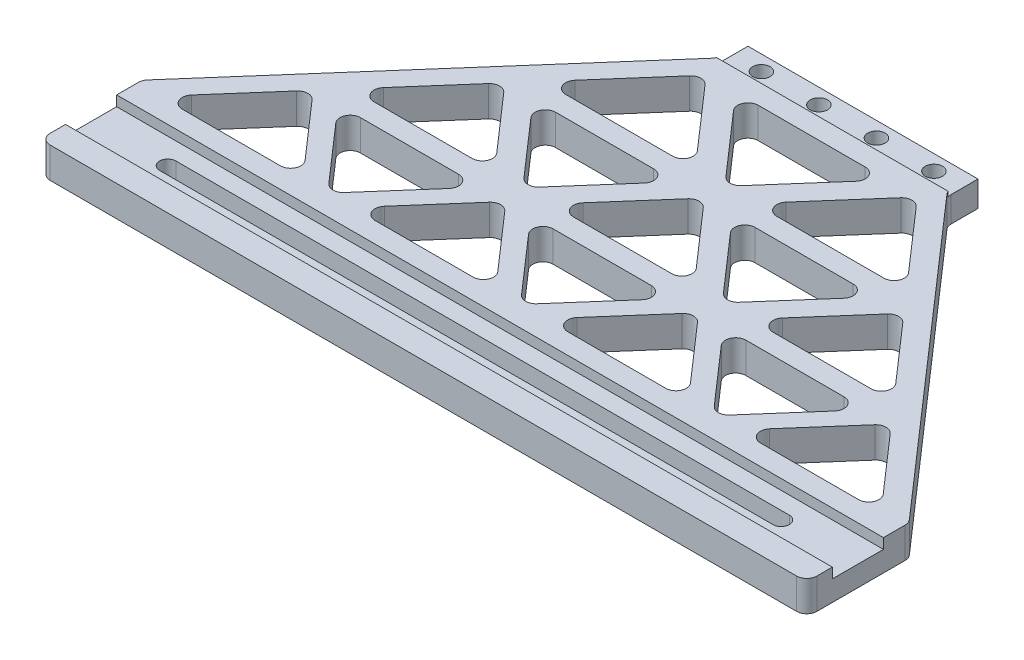
SolidWorks part; units mm, degrees
material "Сплав 2024"
ref_plane "Спереди" through (0, 0, 0) normal (0, 0, 1) x (1, 0, 0)
ref_plane "Сверху" through (0, 0, 0) normal (0, 1, 0) x (1, 0, 0)
ref_plane "Справа" through (0, 0, 0) normal (1, 0, 0) x (0, 0, -1)
sketch "Эскиз1" plane through (0, 0, 0) normal (0, 1, 0) x (1, 0, 0)
  line L0 (-22.5, 0) -> (22.5, 0) construction
  line L1 (-22.5, 3) -> (22.5, 3)
  line L2 (-22.5, 3) -> (-22.5, -3)
  line L3 (-22.5, -3) -> (22.5, -3) construction
  line L4 (22.5, 3) -> (22.5, -3)
  line L5 (-22.5, 3) -> (22.5, -3) construction
  line L6 (-22.5, -3) -> (22.5, 3) construction
  line L7 (0, 3) -> (0, -3) construction
  line L8 (-22.5, -3) -> (-75, -63)
  line L9 (-75, -63) -> (-75, -83)
  line L10 (-75, -83) -> (75, -83)
  line L11 (75, -83) -> (75, -63)
  line L12 (75, -63) -> (22.5, -3)
  line L13 (0, -3) -> (0, -163) construction
  line L14 (75, -63) -> (-75, -63) construction
  line L15 (-16.875, 3) -> (-16.875, -3) construction
  line L16 (-11.25, 3) -> (-11.25, -3) construction
  line L17 (-5.625, 3) -> (-5.625, -3) construction
  line L18 (0, 3) -> (0, -3) construction
  line L19 (5.625, 3) -> (5.625, -3) construction
  line L20 (11.25, 3) -> (11.25, -3) construction
  line L21 (16.875, 3) -> (16.875, -3) construction
  point P0 (0, 0)
  point P10 (0, -83)
  dimension "D1" = 45
  dimension "D2" = 6
  dimension "D3" = 150
  dimension "D4" = 80
  dimension "D5" = 20
  dimension "D6" = 5.625
  dimension "D7" = 5.625
  dimension "D8" = 5.625
  dimension "D9" = 5.625
  dimension "D10" = 5.625
  dimension "D11" = 5.625
  dimension "D12" = 5.625
extrude "Бобышка-Вытянуть1" add sketch "Эскиз1" along normal blind 6
sketch "Эскиз2" plane through (0, 6, 0) normal (0, 1, 0) x (1, 0, 0)
  line L0 (75, -83) -> (75, -63) construction
  line L1 (-75, -78) -> (75, -78)
  line L2 (-75, -78) -> (-75, -68)
  line L3 (-75, -68) -> (75, -68)
  line L4 (75, -78) -> (75, -68)
  line L5 (-75, -83) -> (75, -83) construction
  dimension "D1" = 10
  dimension "D2" = 5
extrude "Вырез-Вытянуть1" cut sketch "Эскиз2" against normal blind 2
fillet "Скругление3" radius 2 2 edges at (22.5, 3, 3) (-22.5, 3, 3)
sketch "Эскиз3" plane through (0, 6, 0) normal (0, 1, 0) x (1, 0, 0)
  line L0 (22.5, 3) -> (-22.5, 3) construction
  line L1 (-23.5, 3) -> (23.5, 3)
  line L2 (-23.5, 3) -> (-23.5, -3)
  line L3 (-23.5, -3) -> (23.5, -3)
  line L4 (23.5, 3) -> (23.5, -3)
  line L5 (-22.5, 3) -> (-22.5, -2.2485) construction
  dimension "D1" = 6
  dimension "D2" = 47
  dimension "D3" = 1
extrude "Вырез-Вытянуть2" cut sketch "Эскиз3" against normal blind 1
hole_wizard "Отверстие с зазором M31" positions "Эскиз8" profile "Эскиз7" hole size "M3" standard "Ansi Metric" end condition through all
sketch "Эскиз8" plane through (0, 0, 0) normal (0, -1, 0) x (-1, 0, 0)
  line L5 (22.5, 0) -> (-22.5, 0) construction
  line L6 (-16.875, 3) -> (-16.875, -3) construction
  line L8 (-5.625, 3) -> (-5.625, -3) construction
  line L10 (5.625, 3) -> (5.625, -3) construction
  line L14 (16.875, 3) -> (16.875, -3) construction
  point P4 (-5.625, 0)
  point P8 (5.625, 0)
  point P12 (16.875, 0)
  point P16 (-16.875, 0)
sketch "Эскиз7" plane through (5.625, 0, 0) normal (1, 0, 0) x (0, 0, -1)
  line L0 (0, 0) -> (0, 6)
  line L1 (0, 6) -> (1.7, 6)
  line L2 (1.7, 6) -> (1.7, 0)
  line L5 (1.7, 0) -> (0, 0)
  line L11 (0, -6.35) -> (0, 107.95) construction
  dimension "Диаметр сквозного отверстия" = 3.4
  dimension "Глубина сквозного отверстия" = 6
sketch "Эскиз9" plane through (0, 4, 0) normal (0, 1, 0) x (1, 0, 0)
  line L0 (-60, -73) -> (60, -73) construction
  line L1 (-60, -71.4) -> (60, -71.4)
  line L2 (-60, -74.6) -> (60, -74.6)
  line L3 (0, -68) -> (0, -78) construction
  line L4 (75, -68) -> (-75, -68) construction
  line L5 (-75, -78) -> (75, -78) construction
  arc A0 (-60, -71.4) -> (-60, -74.6) centre (-60, -73) ccw
  arc A1 (60, -74.6) -> (60, -71.4) centre (60, -73) ccw
  point P2 (0, -73)
  dimension "D1" = 1.6
  dimension "D2" = 120
extrude "Вырез-Вытянуть3" cut sketch "Эскиз9" against normal through all
sketch "Эскиз10" plane through (0, 6, 0) normal (0, 1, 0) x (1, 0, 0)
  line L0 (-2.3315, 13.9753) -> (-85.5296, -81.1082) construction
  line L1 (-1.4219, 18.2649) -> (84.9093, -80.3992) construction
  line L2 (-75, -64) -> (75, -64) construction
  line L3 (-22.9948, -3.5655) -> (-75, -63) construction
  line L4 (75, -63) -> (22.9948, -3.5655) construction
  line L5 (75, -68) -> (-75, -68) construction
  line L6 (-36.0661, -7) -> (36.2465, -7) construction
  line L7 (-22.6465, -3) -> (22.6465, -3) construction
  line L8 (-66.3605, -48) -> (66.7235, -48) construction
  line L9 (-59.8686, -44) -> (61.8546, -44) construction
  line L10 (-43.099, -28) -> (53.3779, -28) construction
  line L11 (36.2465, -24) -> (-41.2957, -24) construction
  line L12 (-70.5599, -64) -> (-56.5599, -48)
  line L13 (-56.5599, -48) -> (-42.5599, -64)
  line L14 (-42.5599, -64) -> (-70.5599, -64)
  line L15 (-51.7099, -48) -> (-37.7099, -64)
  line L16 (-37.7099, -64) -> (-23.7099, -48)
  line L17 (-23.7099, -48) -> (-51.7099, -48)
  line L18 (-18.8599, -48) -> (-32.8599, -64)
  line L19 (-32.8599, -64) -> (-4.8599, -64)
  line L20 (-4.8599, -64) -> (-18.8599, -48)
  line L21 (-14.0099, -48) -> (-0.0099, -64)
  line L22 (-0.0099, -64) -> (13.9901, -48)
  line L23 (13.9901, -48) -> (-14.0099, -48)
  line L24 (18.8401, -48) -> (4.8401, -64)
  line L25 (4.8401, -64) -> (32.8401, -64)
  line L26 (32.8401, -64) -> (18.8401, -48)
  line L27 (23.6901, -48) -> (37.6901, -64)
  line L28 (37.6901, -64) -> (51.6901, -48)
  line L29 (51.6901, -48) -> (23.6901, -48)
  line L31 (42.5401, -64) -> (70.5401, -64)
  line L32 (70.5401, -64) -> (56.5401, -48)
  line L33 (56.5401, -48) -> (42.5401, -64)
  line L34 (-75, -63) -> (-75, -68) construction
  line L35 (75, -68) -> (75, -63) construction
  line L36 (-53.0599, -44) -> (-39.0599, -28)
  line L37 (-39.0599, -28) -> (-25.0599, -44)
  line L38 (-25.0599, -44) -> (-53.0599, -44)
  line L39 (-33.5455, -28) -> (-19.5455, -44)
  line L40 (-19.5455, -44) -> (-5.5455, -28)
  line L41 (-5.5455, -28) -> (-33.5455, -28)
  line L42 (-0.0312, -28) -> (-14.0312, -44)
  line L43 (-14.0312, -44) -> (13.9688, -44)
  line L44 (13.9688, -44) -> (-0.0312, -28)
  line L45 (5.4832, -28) -> (19.4832, -44)
  line L46 (19.4832, -44) -> (33.4832, -28)
  line L47 (33.4832, -28) -> (5.4832, -28)
  line L48 (24.9976, -44) -> (38.9976, -28)
  line L49 (38.9976, -28) -> (52.9976, -44)
  line L50 (52.9976, -44) -> (24.9976, -44)
  line L51 (-35.5599, -24) -> (-20.6849, -7)
  line L52 (-20.6849, -7) -> (-5.8099, -24)
  line L53 (-5.8099, -24) -> (-35.5599, -24)
  line L54 (-14.9048, -7) -> (-0.0298, -24)
  line L55 (-0.0298, -24) -> (14.8452, -7)
  line L56 (14.8452, -7) -> (-14.9048, -7)
  line L57 (20.6254, -7) -> (5.7504, -24)
  line L58 (5.7504, -24) -> (35.5004, -24)
  line L59 (35.5004, -24) -> (20.6254, -7)
  dimension "D1" = 4
  dimension "D2" = 4
  dimension "D3" = 4
  dimension "D4" = 4
  dimension "D5" = 4
  dimension "D6" = 4
  dimension "D7" = 48.814
  dimension "D8" = 48.814
  dimension "D9" = 57
  dimension "D10" = 16
  dimension "D11" = 16
  dimension "D12" = 82.372
  dimension "D13" = 82.372
  dimension "D14" = 82.372
  dimension "D15" = 82.372
  dimension "D16" = 3.65
  dimension "D17" = 3.65
  dimension "D18" = 82.372
  dimension "D19" = 82.372
  dimension "D20" = 3.65
  dimension "D21" = 3.65
  dimension "D22" = 3.65
  dimension "D23" = 3.65
  dimension "D24" = 82.372
  dimension "D25" = 4.15
  dimension "D26" = 4.15
  dimension "D27" = 4.15
  dimension "D28" = 82.372
  dimension "D29" = 82.372
  dimension "D30" = 82.372
  dimension "D31" = 82.372
  dimension "D32" = 4.15
  dimension "D33" = 82.372
  dimension "D34" = 82.372
  dimension "D35" = 82.372
  dimension "D36" = 82.372
  dimension "D37" = 4.35
  dimension "D38" = 4.35
extrude "Вырез-Вытянуть4" cut sketch "Эскиз10" against normal up to next
fillet "Скругление1" radius 2 49 edges at (18.8401, 3, 48) (23.6901, 3, 48) (-14.0099, 3, 48) (-51.7099, 3, 48) (-33.5455, 3, 28) (5.4832, 3, 28) (5.7504, 3, 24) (24.9976, 3, 44) (4.8401, 3, 64) (-32.8599, 3, 64) (-70.5599, 3, 64) (-14.0312, 3, 44) (-53.0599, 3, 44) (-35.5599, 3, 24) (-42.5599, 3, 64) (-25.0599, 3, 44) (-4.8599, 3, 64) (35.5004, 3, 24) (52.9976, 3, 44) (70.5401, 3, 64) (32.8401, 3, 64) (13.9688, 3, 44) (-5.8099, 3, 24) (-0.0298, 3, 24) (-37.7099, 3, 64) (-0.0099, 3, 64) (19.4832, 3, 44) (37.6901, 3, 64) (56.5401, 3, 48) (38.9976, 3, 28) (-0.0312, 3, 28) (-18.8599, 3, 48) (-56.5599, 3, 48) (-39.0599, 3, 28) (-20.6849, 3, 7) (20.6254, 3, 7) (-23.7099, 3, 48) (13.9901, 3, 48) (-5.5455, 3, 28) (51.6901, 3, 48) (33.4832, 3, 28) (14.8452, 3, 7) (-75, 3, 63) (-75, 3, 83) (75, 3, 83) (75, 3, 63) (-19.5455, 3, 44) (42.5401, 3, 64) (-14.9048, 3, 7)
fillet "Скругление2" [suppressed] radius 2
equation "\"D6@Эскиз1\"=\"D1@Эскиз1\"/8"
equation "\"D7@Эскиз1\"=\"D6@Эскиз1\""
equation "\"D8@Эскиз1\"=\"D6@Эскиз1\""
equation "\"D9@Эскиз1\"=\"D6@Эскиз1\""
equation "\"D13@Эскиз10\"=\"D12@Эскиз10\""
equation "\"D14@Эскиз10\"=\"D12@Эскиз10\""
equation "\"D15@Эскиз10\"=\"D12@Эскиз10\""
equation "\"D18@Эскиз10\"=\"D12@Эскиз10\""
equation "\"D19@Эскиз10\"=\"D12@Эскиз10\""
equation "\"D24@Эскиз10\"=\"D12@Эскиз10\""
equation "\"D17@Эскиз10\"=\"D16@Эскиз10\""
equation "\"D23@Эскиз10\"=\"D16@Эскиз10\""
equation "\"D22@Эскиз10\"=\"D16@Эскиз10\""
equation "\"D20@Эскиз10\"=\"D16@Эскиз10\""
equation "\"D21@Эскиз10\"=\"D16@Эскиз10\""
equation "\"D28@Эскиз10\"=\"D12@Эскиз10\""
equation "\"D29@Эскиз10\"=\"D28@Эскиз10\""
equation "\"D30@Эскиз10\"=\"D28@Эскиз10\""
equation "\"D31@Эскиз10\"=\"D28@Эскиз10\""
equation "\"D32@Эскиз10\"=\"D25@Эскиз10\""
equation "\"D26@Эскиз10\"=\"D25@Эскиз10\""
equation "\"D27@Эскиз10\"=\"D25@Эскиз10\""
equation "\"D33@Эскиз10\"=\"D28@Эскиз10\""
equation "\"D34@Эскиз10\"=\"D12@Эскиз10\""
equation "\"D35@Эскиз10\"=\"D34@Эскиз10\""
equation "\"D36@Эскиз10\"=\"D34@Эскиз10\""
equation "\"D38@Эскиз10\"=\"D37@Эскиз10\""
equation "\"D10@Эскиз1\"=\"D6@Эскиз1\""
equation "\"D11@Эскиз1\"=\"D6@Эскиз1\""
equation "\"D12@Эскиз1\"=\"D6@Эскиз1\""
